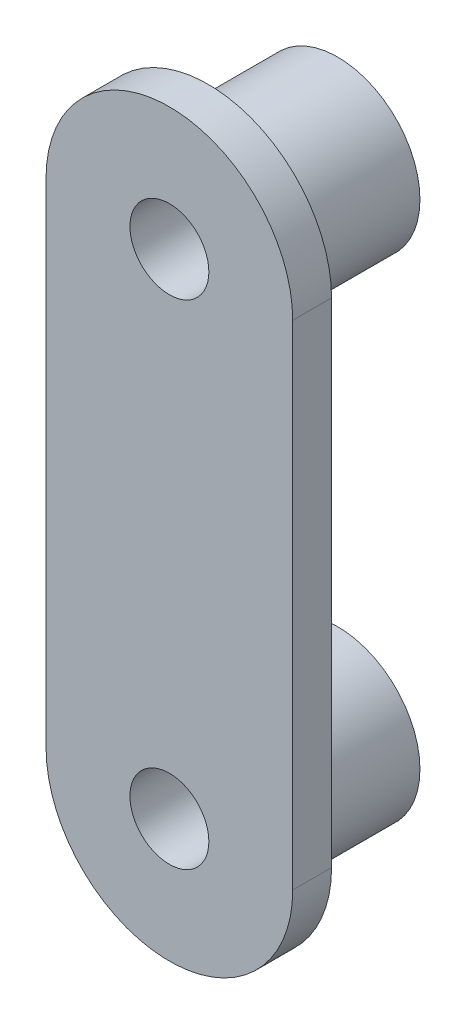
SolidWorks part; units mm, degrees
ref_plane "Front Plane" through (0, 0, 0) normal (0, 0, 1) x (1, 0, 0)
ref_plane "Top Plane" through (0, 0, 0) normal (0, 1, 0) x (1, 0, 0)
ref_plane "Right Plane" through (0, 0, 0) normal (1, 0, 0) x (0, 0, -1)
sketch "Sketch3" plane through (0, 0, 0) normal (0, 0, 1) x (1, 0, 0)
  line L8 (-7.9375, 22.225) -> (-7.9375, -16.9164)
  line L9 (-7.9375, -16.9164) -> (7.9375, -16.9164)
  line L10 (7.9375, -16.9164) -> (7.9375, 22.225)
  line L11 (7.9375, 22.225) -> (-7.9375, 22.225)
  circle A2 centre (4.7625, 19.05) radius 1.5875
  circle A3 centre (4.7625, 0) radius 1.5875
sketch "Sketch1" plane through (0, 0, 0) normal (0, 0, 1) x (1, 0, 0)
  line L0 (1.5875, 0) -> (7.9375, 0) construction
  line L1 (4.7625, -3.175) -> (4.7625, 3.175) construction
  line L2 (4.7625, 0) -> (4.7625, -19.05) construction
  line L3 (9.525, 0) -> (9.525, -19.05)
  line L4 (0, 0) -> (0, -19.05)
  line L5 (4.7625, 0) -> (4.7625, -3.175)
  line L7 (4.7625, -22.225) -> (4.7625, -15.875) construction
  line L8 (4.7625, -15.875) -> (4.7625, -19.05)
  line L20 (4.7625, 0) -> (4.7625, -19.05)
  circle A0 centre (4.7625, 0) radius 3.175
  circle A1 centre (4.7625, -19.05) radius 3.175
  arc A2 (9.525, 0) -> (0, 0) centre (4.7625, 0) ccw
  arc A3 (0, -19.05) -> (9.525, -19.05) centre (4.7625, -19.05) ccw
  circle A4 centre (4.7625, 0) radius 1.524
  circle A5 centre (4.7625, -19.05) radius 1.524
  point P0 (0, 0)
  point P1 (4.7625, -9.525)
  dimension "D2" = 9.525
  dimension "D1" = 19.05
extrude "Boss-Extrude1" add sketch "Sketch1" along normal blind 1.5 contours A1 L5 A0 | A4 A0 | L5 | L5 | A5 A1 | A1 A0 L5 | A0 region at (9.2238, -9.525, 0) region at (2.5809, 2.1816, 0) region at (6.9441, -16.8684, 0)
extrude "Boss-Extrude2" add sketch "Sketch1<7>" against normal blind 5 contours A4 A0 | A5 A1 region at (2.5809, 2.1816, 0) region at (6.9441, -16.8684, 0)
sketch "Sketch1<7>" plane through (0, 0, 0) normal (0, 0, 1) x (1, 0, 0) same geometry as "Sketch1"
